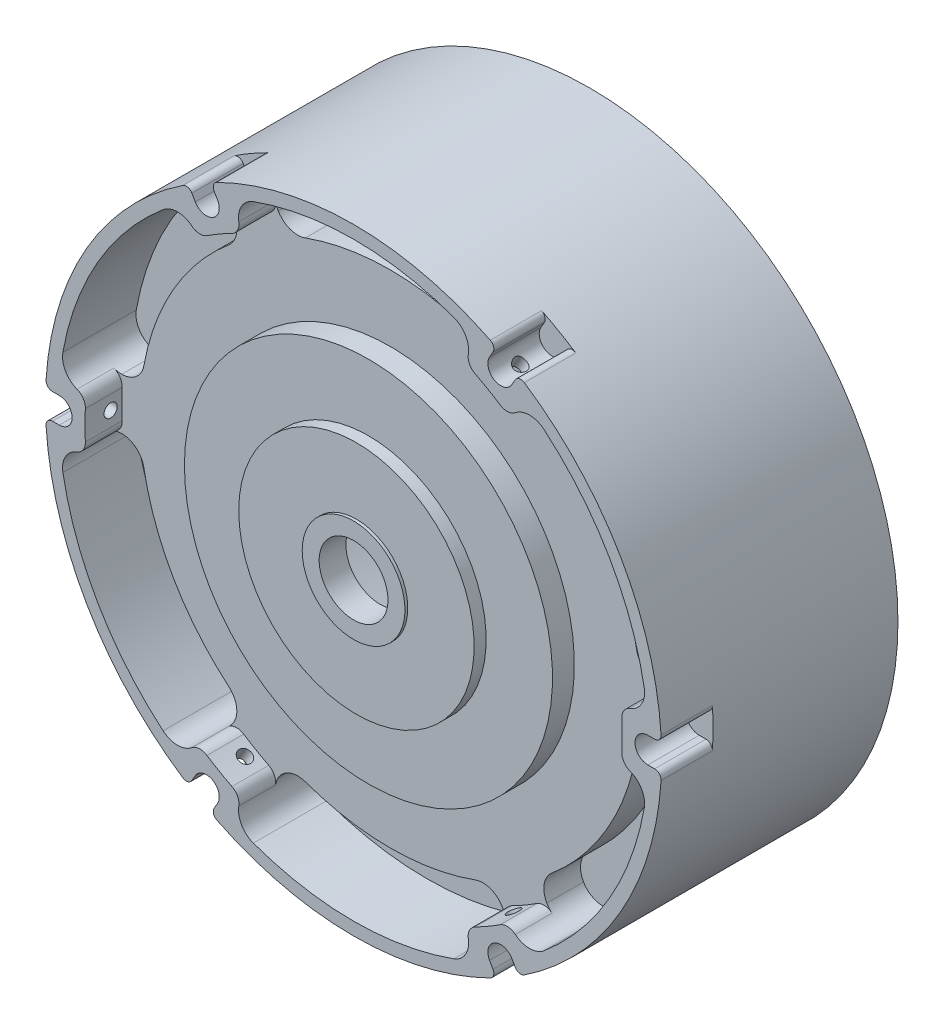
SolidWorks part; units mm, degrees
material "6061-T6 (SS)"
ref_plane "Front Plane" through (0, 0, 0) normal (0, 0, 1) x (1, 0, 0)
ref_plane "Top Plane" through (0, 0, 0) normal (0, 1, 0) x (1, 0, 0)
ref_plane "Right Plane" through (0, 0, 0) normal (1, 0, 0) x (0, 0, -1)
sketch "Sketch2" plane through (0, 0, 0) normal (0, 1, 0) x (1, 0, 0)
  line L0 (0, 6.35) -> (0, 0)
  line L2 (-76.2, 0) -> (-76.2, 41.275)
  line L3 (-76.2, 41.275) -> (-69.85, 41.275) construction
  line L4 (-69.85, 41.275) -> (-34.925, 41.275) construction
  line L5 (-34.925, 41.275) -> (0, 41.275) construction
  line L6 (-76.2, 0) -> (-73.025, 0)
  line L13 (-73.025, 0) -> (-73.025, 18.1545)
  line L14 (-73.025, 18.1545) -> (-61.9125, 18.1545)
  line L15 (-61.9125, 18.1545) -> (-61.9125, 9.0909)
  line L16 (-61.9125, 9.0909) -> (-45.5083, 9.0909)
  line L17 (-45.5083, 9.0909) -> (-45.5083, 3.6843)
  line L18 (-45.5083, 3.6843) -> (-29.1042, 3.6843)
  line L19 (-29.1042, 3.6843) -> (-29.1042, 0.7103)
  line L20 (0, 41.275) -> (0, 6.35) construction
  line L21 (-45.5083, 9.0909) -> (0, 41.275) construction
  line L22 (-61.9125, 18.1545) -> (0, 41.275) construction
  line L23 (0, 41.275) -> (-29.1042, 3.6843) construction
  line L24 (-29.1042, 0.7103) -> (-12.7, 0.7103)
  line L25 (-12.7, 0.7103) -> (-12.7, 0)
  line L26 (-12.7, 0) -> (0, 0)
  line L27 (0, 41.275) -> (-12.7, 0.7103) construction
  line L28 (-69.85, 41.275) -> (-69.85, 58.42)
  line L29 (-69.85, 58.42) -> (-76.2, 58.42)
  line L30 (-76.2, 58.42) -> (-76.2, 41.275)
  ellipse E0 centre (0, 41.275) end of major axis (69.85, 41.275) minor radius 34.925 construction
  ellipse E1 centre (0, 41.275) end of major axis (69.85, 41.275) minor radius 34.925 (-69.85, 41.275) -> (0, 6.35) ccw
  point P2 (-10.8028, 6.7702)
  point P7 (-55.9638, 20.376)
  point P16 (-25.2167, 8.7053)
  point P18 (-40.3238, 12.7574)
  dimension "D3" = 6.35
  dimension "D6" = 6.35
  dimension "D7" = 6.35
  dimension "D11" = 58.42
  dimension "D2" = 76.2
  dimension "D4" = 11.1125
  dimension "D5" = 3.175
  dimension "D8" = 6.35
  dimension "D9" = 6.35
  dimension "D10" = 12.7
  dimension "D12" = 6.35
  dimension "D13" = 52.07
  dimension "D14" = 17.145
revolve "Revolve1" add sketch "Sketch2" angle 360 about L20
sketch "Sketch5" plane through (0, 0, 0) normal (0, 0, 1) x (1, 0, 0)
  circle A0 centre (0, 0) radius 8.509
  dimension "D1" = 17.018
extrude "Cut-Extrude2" cut sketch "Sketch5" against normal through all
sketch "Sketch11" plane through (0, 0, 0) normal (0, 0, 1) x (1, 0, 0)
  line L0 (-76.1338, 3.175) -> (-72.771, 3.175)
  line L1 (-76.1338, -3.175) -> (-72.771, -3.175)
  line L2 (-75.935, 6.35) -> (-61.586, 6.35)
  line L3 (-61.586, 6.35) -> (-61.586, -6.35)
  line L4 (-61.586, -6.35) -> (-75.935, -6.35)
  circle A0 centre (0, 0) radius 76.2 construction
  arc A1 (-72.771, -3.175) -> (-72.771, 3.175) centre (-72.771, 0) ccw
  arc A2 (-76.1338, 3.175) -> (-76.1338, -3.175) centre (0, 0) ccw
  circle A3 centre (0, 0) radius 61.9125 construction
  circle A4 centre (0, 0) radius 61.9125 construction
  arc A5 (-76.1338, -3.175) -> (-75.935, -6.35) centre (-76.3902, -4.7848) cw
  arc A6 (-75.935, 6.35) -> (-76.1338, 3.175) centre (-76.5368, 4.794) cw
  point P8 (-69.596, 0)
  point P20 (-76.2, 0)
  circle M6 centre (0, 0) radius 73.025
  circle M7 centre (0, 0) radius 76.2
  dimension "D1" = 6.35
  dimension "D2" = 3.175
  dimension "D3" = 6.604
extrude "Boss-Extrude2" add sketch "Sketch11" against normal up to surface (18.1545 mm away) contours A1 L4 L3 L2 M6 | A1 M6 | A1 L0 L1 M6 M7 region at (-74.59, 0, 0) region at (-66.6747, 0, 0) region at (-71.5476, 0, 0) up to face at (-61.9125, 0, -18.1545)
sketch "Sketch12" plane through (0, 0, 0) normal (0, 0, 1) x (1, 0, 0)
  line L0 (-76.1338, 3.175) -> (-72.771, 3.175)
  line L1 (-76.1338, -3.175) -> (-72.771, -3.175)
  arc A1 (-72.771, 3.175) -> (-72.771, -3.175) centre (-72.771, 0) cw
  arc A3 (-76.1338, -3.175) -> (-76.1338, 3.175) centre (-76.1338, 0) cw
  point P10 (-69.596, 0)
extrude "Cut-Extrude4" cut sketch "Sketch12" against normal blind 12.7
hole_wizard "#30 (0.1285) Diameter Hole1" positions "Sketch13" profile "Sketch14" hole size "#30" standard "ANSI Inch" end condition through all
sketch "Sketch13" plane through (-61.586, 0, 0) normal (1, 0, 0) x (0, 0, -1)
  line L0 (0, 6.35) -> (0, -6.35) construction
  point P0 (6.35, 0)
  dimension "D1" = 6.35
sketch "Sketch14" plane through (-61.586, 0, -6.35) normal (0, 1, 0) x (0, 0, -1)
  line L0 (0, 0) -> (0, 14.614)
  line L1 (0, 14.614) -> (1.6319, 14.614)
  line L2 (1.6319, 14.614) -> (1.6319, 0)
  line L5 (1.6319, 0) -> (0, 0)
  line L11 (0, -6.35) -> (0, 107.95) construction
  dimension "Thru Hole Dia." = 3.2639
  dimension "Thru Hole Depth" = 14.614
fillet "Fillet3" radius 5.5562 4 edges at (-72.7484, -6.35, -9.0772) (-72.7484, 6.35, -9.0772) (-61.586, -6.35, -13.6227) (-61.586, 6.35, -13.6227)
fillet "Fillet5" radius 1.5875 2 edges at (-76.1338, -3.175, -6.35) (-76.1338, 3.175, -6.35)
pattern_circular "CirPattern3" count 6 over 360 about axis through (0, 0, 0) along (0, 0, -1) of "Boss-Extrude2", "Cut-Extrude4", "#30 (0.1285) Diameter Hole1", "Fillet3", "Fillet5"
sketch "Sketch15" plane through (0, 0, 0) normal (0, 0, 1) x (1, 0, 0)
  line L0 (-61.586, 6.35) -> (-61.586, -6.35) construction
  circle A0 centre (0, 0) radius 61.586
  circle A1 centre (0, 0) radius 66.421
  point P4 (-66.421, 0)
  dimension "D1" = 3.175
extrude "Cut-Extrude6" cut sketch "Sketch15" against normal up to surface (9.0909 mm away) up to face at (-45.5083, 0, -9.0909)
fillet "Fillet6" radius 3.175 12 edges at (-66.1168, 6.35, -4.5454) (-66.1168, -6.35, -4.5454) (38.5576, 54.0838, -4.5454) (-38.5576, 54.0838, -4.5454) (-27.5591, 60.4338, -4.5454) (27.5591, 60.4338, -4.5454) (66.1168, -6.35, -4.5454) (66.1168, 6.35, -4.5454) (38.5576, -54.0838, -4.5454) (27.5591, -60.4338, -4.5454) (-27.5591, -60.4338, -4.5454) (-38.5576, -54.0838, -4.5454)
equation "\"beams\"= 6"
equation "\"D1@CirPattern3\"=\"beams\""
